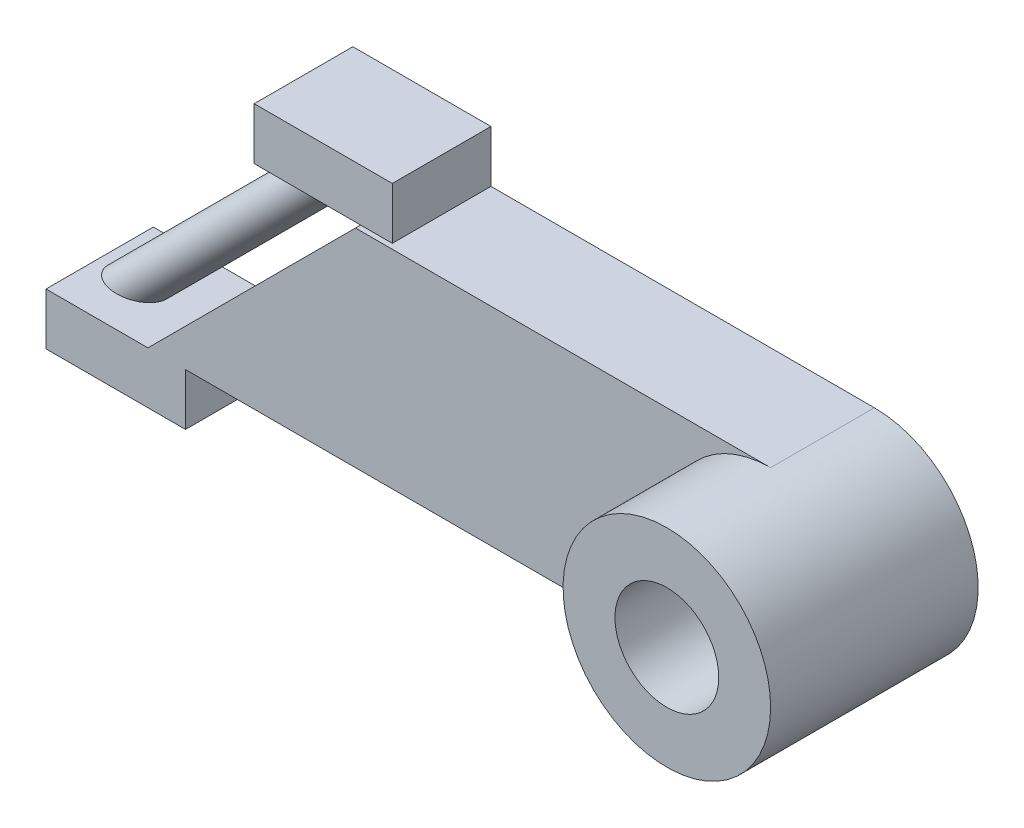
SolidWorks part; units mm, degrees
ref_plane "Piano frontale" through (0, 0, 0) normal (0, 0, 1) x (1, 0, 0)
ref_plane "Piano superiore" through (0, 0, 0) normal (0, 1, 0) x (1, 0, 0)
ref_plane "Piano destro" through (0, 0, 0) normal (1, 0, 0) x (0, 0, -1)
sketch "Schizzo1" plane through (0, 0, 0) normal (0, 0, 1) x (1, 0, 0)
  line L0 (0, 0) -> (-20, 0)
  line L1 (-20, 0) -> (-10, 10)
  line L2 (-10, 10) -> (10, 10)
  line L4 (10, 0) -> (0, 0)
  arc A0 (10, 0) -> (10, 10) centre (10, 5) ccw
  dimension "D6" = 10
  dimension "D1" = 20
  dimension "D2" = 10
  dimension "D3" = 10
  dimension "D4" = 0
  dimension "D5" = 20
extrude "Estrusione-Estrusione1" add sketch "Schizzo1" along normal blind 5 contours L2 A0 L4 L0 L1
sketch "Schizzo3" plane through (0, 0, 5) normal (0, 0, 1) x (1, 0, 0)
  arc A0 (10, 0) -> (10, 10) centre (10, 5) ccw construction
  arc A1 (10, 0) -> (10, 10) centre (10, 5) ccw construction
  circle A2 centre (10, 5) radius 5
  circle A3 centre (10, 5) radius 2.5
extrude "Estrusione-Estrusione3" add sketch "Schizzo3" along normal blind 5
ref_plane "Piano1" through (-1.4208, -1.4208, 0) normal (0.7071, 0.7071, 0) x (0.33, -0.33, -0.8844)
sketch "Schizzo6" plane through (-1.4208, -1.4208, 0) normal (0.7071, 0.7071, 0) x (0.33, -0.33, -0.8844)
  circle A0 centre (-9.8026, 13.2172) radius 1
  circle A1 centre (-9.8026, 13.2172) radius 1 construction
  dimension "D1" = 2
  dimension "D2" = 0
extrude "Estrusione-Estrusione4" add sketch "Schizzo6" against normal blind 18 separate body
sketch "Schizzo7" plane through (0, 10, 0) normal (0, 1, 0) x (1, 0, 0)
  line L0 (-10, 0) -> (10, 0) construction
  line L1 (-8.4737, 0) -> (-15.1262, 0)
  line L2 (-8.4737, 0) -> (-8.4737, -4.7534)
  line L3 (-8.4737, -4.7534) -> (-15.1262, -4.7534)
  line L4 (-15.1262, 0) -> (-15.1262, -4.7534)
  line L5 (-12.4195, -5.7016) -> (-34.8381, 2.1516) construction
extrude "Estrusione-Estrusione5" add sketch "Schizzo7" along normal blind 2.5 contours L2 L3 L4 L1
sketch "Schizzo8" plane through (0, 0, 0) normal (0, -1, 0) x (1, 0, 0)
  line L0 (10, 5) -> (-20, 5) construction
  line L1 (-18.1896, 5) -> (-24.9107, 5)
  line L2 (-18.1896, 5) -> (-18.1896, -0.1711)
  line L3 (-18.1896, -0.1711) -> (-24.9107, -0.1711)
  line L4 (-24.9107, 5) -> (-24.9107, -0.1711)
  line L5 (-33.7659, -3.2731) -> (-20.7692, 1.2797) construction
extrude "Estrusione-Estrusione6" add sketch "Schizzo8" along normal blind 2.5
